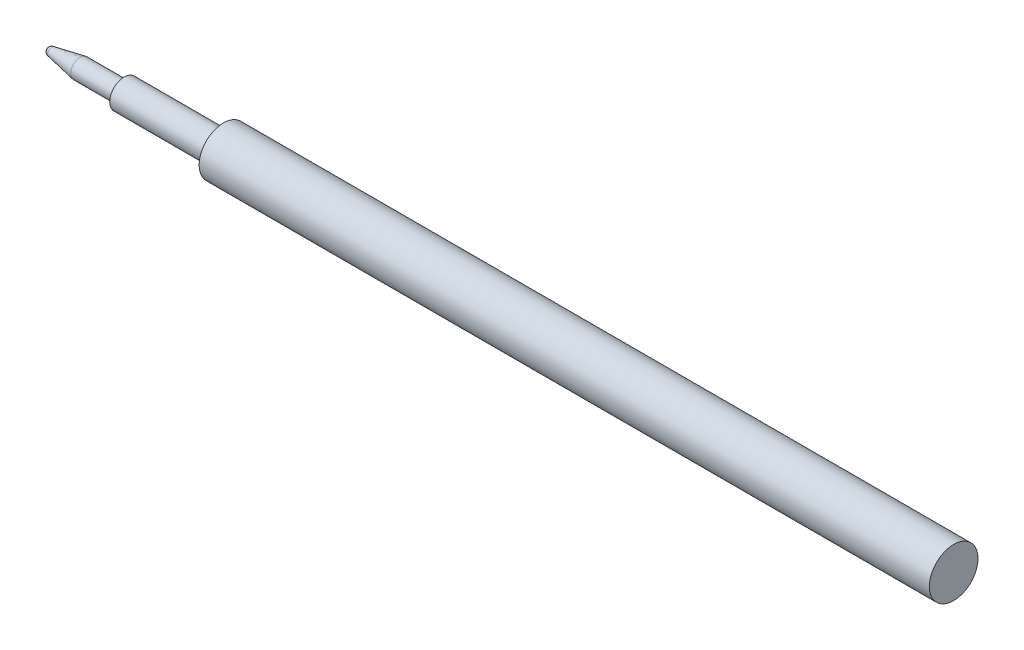
SolidWorks part; units mm, degrees
ref_plane "Front Plane" through (0, 0, 0) normal (0, 0, 1) x (1, 0, 0)
ref_plane "Top Plane" through (0, 0, 0) normal (0, 1, 0) x (1, 0, 0)
ref_plane "Right Plane" through (0, 0, 0) normal (1, 0, 0) x (0, 0, -1)
sketch "Sketch1" plane through (0, 0, 0) normal (0, 0, 1) x (1, 0, 0)
  line L0 (-90, 0) -> (-102.25, 0)
  line L1 (0, 0) -> (-90, 0)
  line L2 (0, 0) -> (0, 3)
  line L3 (0, 3) -> (-90, 3)
  line L4 (-90, 0) -> (-90, 3)
  line L5 (-102.25, 0) -> (-102.25, 1.77)
  line L6 (-102.25, 1.77) -> (-90, 1.77)
  line L7 (-102.25, 0) -> (-94.74, 0)
  line L10 (-94.74, 0) -> (-100.74, 0)
  line L13 (-100.74, 0) -> (-107.67, 0)
  line L14 (-107.67, 0) -> (-107.67, 1.16)
  line L15 (-107.67, 1.16) -> (-102.25, 1.16)
  line L16 (-107.67, 1.16) -> (-111.17, 0.5)
  line L17 (-111.17, 0.5) -> (-111.17, 0)
  line L18 (-111.17, 0) -> (-107.67, 0)
  line L19 (-111.17, 0) -> (-111.67, 0)
  arc A0 (-111.67, 0) -> (-111.17, 0.5) centre (-111.17, 0) cw
  point P10 (-102.25, 1.25)
  dimension "D1" = 3
  dimension "D2" = 90
  dimension "D3" = 1.77
  dimension "D4" = 12.25
  dimension "D8" = 1.16
  dimension "D9" = 5.42
  dimension "D10" = 3.5
  dimension "D11" = 0.5
  dimension "D12" = 0.5
revolve "Revolve1" add sketch "Sketch1" angle 360 about L1 region at (-45, 1.5, 0) region at (-96.125, 0.885, 0) region at (-104.96, 0.58, 0) region at (-109.1881, 0.4369, 0) region at (-111.3822, 0.2122, 0)
